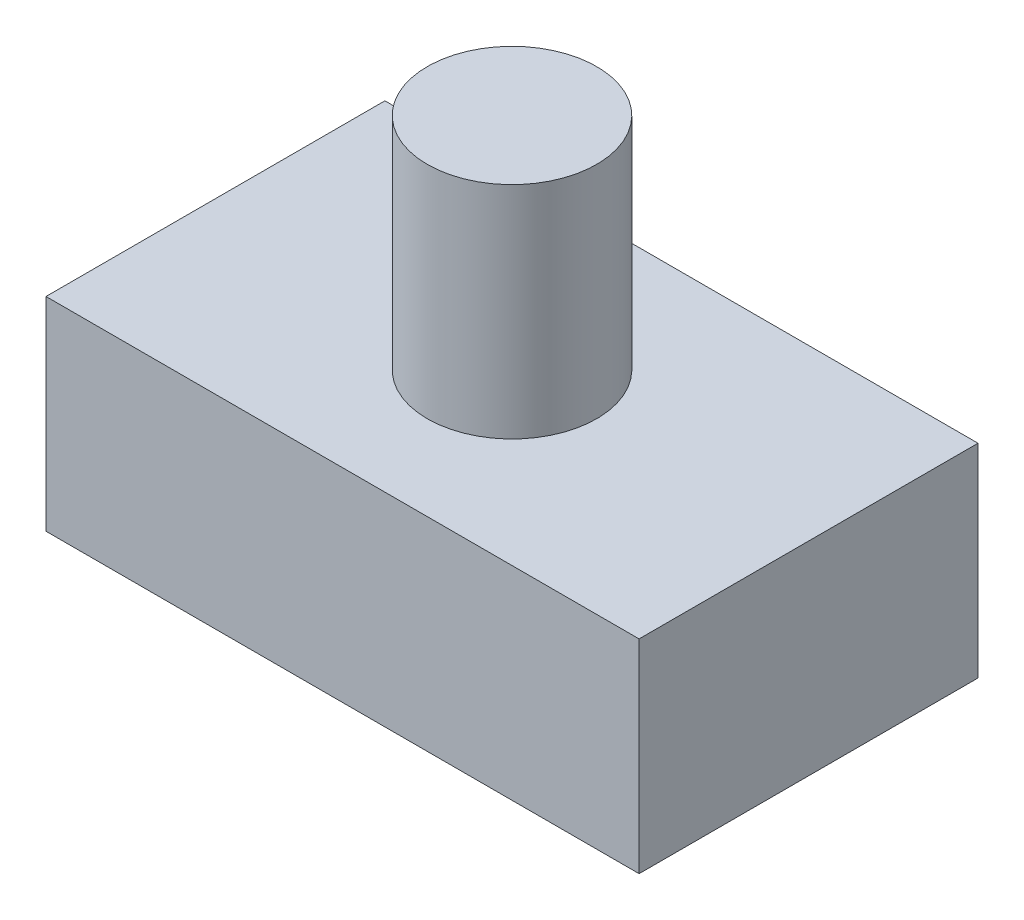
SolidWorks part; units mm, degrees
ref_plane "Front Plane" through (0, 0, 0) normal (0, 0, 1) x (1, 0, 0)
ref_plane "Top Plane" through (0, 0, 0) normal (0, 1, 0) x (1, 0, 0)
ref_plane "Right Plane" through (0, 0, 0) normal (1, 0, 0) x (0, 0, -1)
sketch "Sketch1" plane through (0, 0, 0) normal (0, 1, 0) x (1, 0, 0)
  line L1 (17.5, -10) -> (-17.5, -10)
  line L2 (17.5, -10) -> (17.5, 10)
  line L3 (17.5, 10) -> (-17.5, 10)
  line L4 (-17.5, -10) -> (-17.5, 10)
  line L5 (17.5, -10) -> (-17.5, 10) construction
  line L6 (17.5, 10) -> (-17.5, -10) construction
  circle A0 centre (0, 0) radius 5
  point P0 (0, 0)
  dimension "D3" = 10
  dimension "D1" = 20
  dimension "D2" = 35
extrude "Boss-Extrude1" add sketch "Sketch1" along normal blind 12 contours A0 | L4 L1 L2 L3 A0 region at (0, 0, 9.5969) region at (0, 0, 0)
extrude "Boss-Extrude2" add sketch "Sketch1<3>" along normal blind 25 contours A0
sketch "Sketch1<3>" plane through (0, 0, 0) normal (0, 1, 0) x (1, 0, 0) same geometry as "Sketch1"
